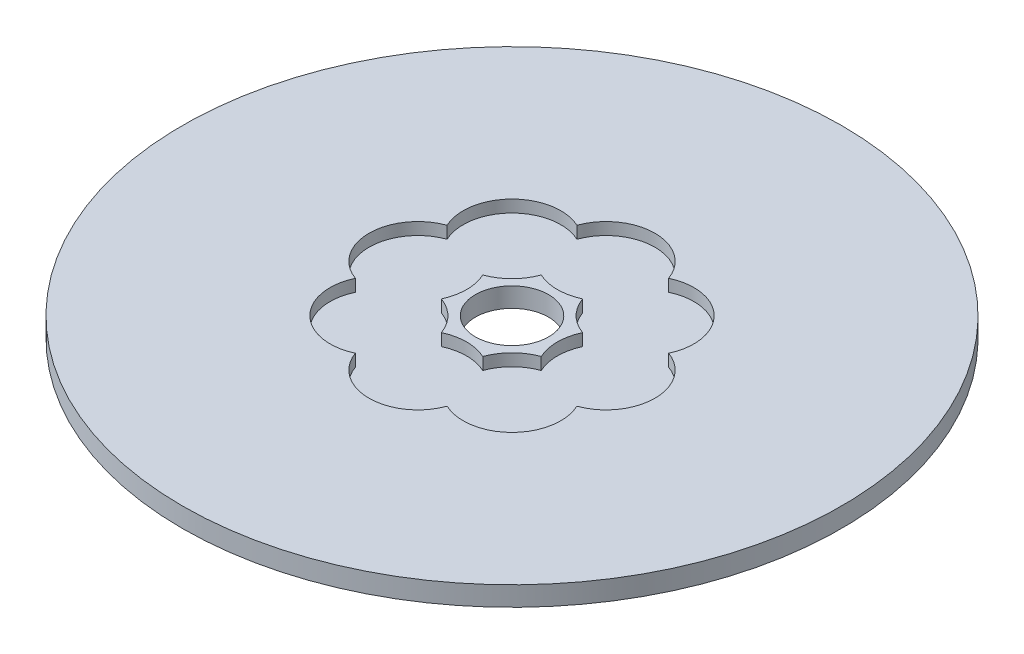
SolidWorks part; units mm, degrees
ref_plane "Front Plane" through (0, 0, 0) normal (0, 0, 1) x (1, 0, 0)
ref_plane "Top Plane" through (0, 0, 0) normal (0, 1, 0) x (1, 0, 0)
ref_plane "Right Plane" through (0, 0, 0) normal (1, 0, 0) x (0, 0, -1)
sketch "Sketch1" plane through (0, 0, 0) normal (0, 1, 0) x (1, 0, 0)
  circle A0 centre (0, 0) radius 67.5
  dimension "FLANGE_OD" = 135
extrude "Boss-Extrude1" add sketch "Sketch1" along normal blind 4
sketch "Sketch2" plane through (0, 0, 0) normal (0, 1, 0) x (1, 0, 0)
  circle A0 centre (0, 0) radius 7.5
  dimension "BORE_D" = 15
extrude "Cut-Extrude1" cut sketch "Sketch2" along normal through all
sketch "Sketch3" plane through (0, 4, 0) normal (0, 1, 0) x (1, 0, 0)
  circle A0 centre (0, 0) radius 19.2804 construction
  circle A1 centre (-19.2804, 0) radius 10
  dimension "BOLT_D" = 20
  dimension "BOLT_PCD" = 38.5608
extrude "Cut-Extrude2" cut sketch "Sketch3" against normal blind 2.4858
pattern_circular "CirPattern1" count 8 over 360 about axis through (0, 0, 0) along (0, 1, 0) of "Cut-Extrude2"
